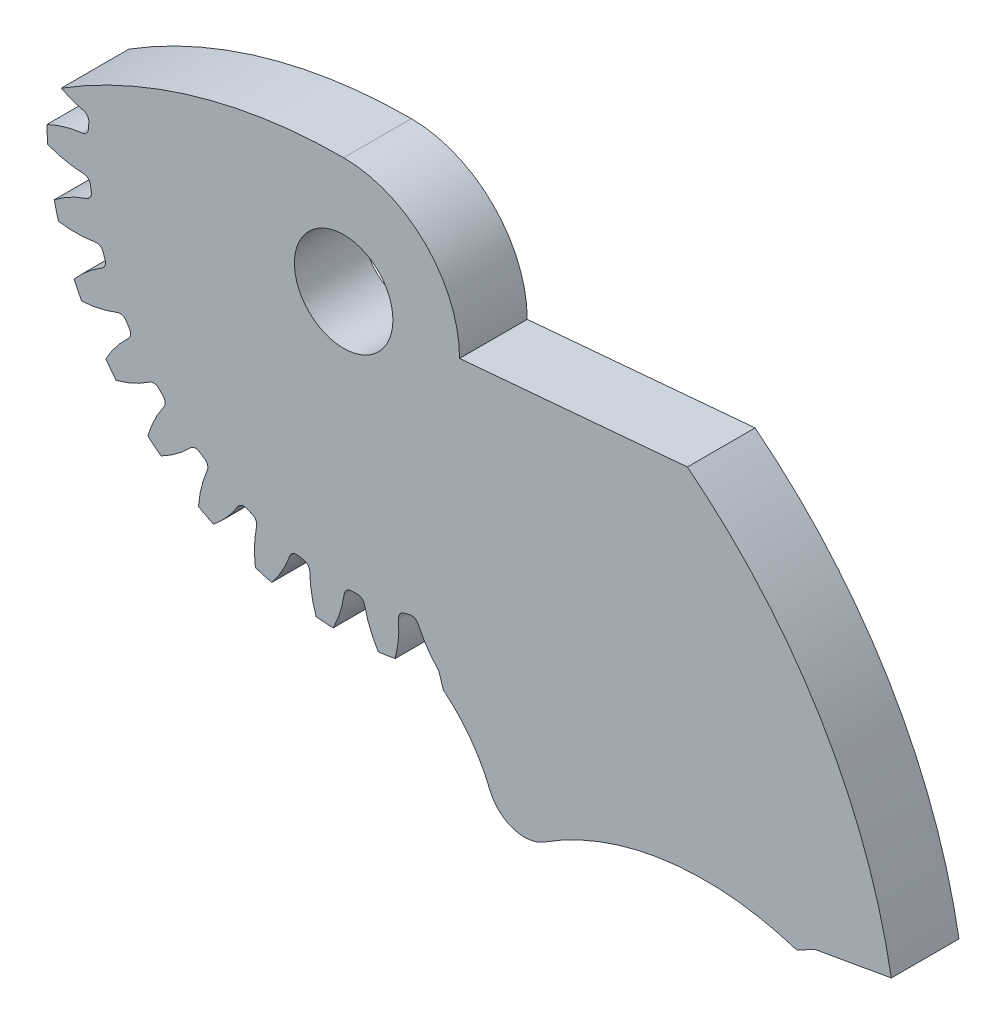
SolidWorks part; units mm, degrees
material "Delrin 2700 NC010, Low Viscosity Acetal Copolymer (SS)"
ref_plane "Front" through (0, 0, 0) normal (0, 0, 1) x (1, 0, 0)
ref_plane "Top" through (0, 0, 0) normal (0, 1, 0) x (1, 0, 0)
ref_plane "Right" through (0, 0, 0) normal (1, 0, 0) x (0, 0, -1)
sketch "Sketch3" plane through (0, 0, 0) normal (0, 0, 1) x (1, 0, 0)
  circle A0 centre (0, 0) radius 40.64
  dimension "od" = 81.28
extrude "gearBody" add sketch "Sketch3" along normal blind 25.4
sketch "Sketch2" plane through (0, 0, 0) normal (0, 0, 1) x (1, 0, 0)
  line L0 (0, 0) -> (34.0786, 14.1158) construction
  line L1 (45.4751, -11.4855) -> (0, 0) construction
  line L2 (0, 0) -> (36.3143, 0) construction
  line L3 (38.0972, -0.458) -> (37.8451, -4.4001) construction
  line L5 (37.9712, -2.4291) -> (0, 0) construction
  line L7 (0, 0) -> (36.8864, 0) construction
  arc A0 (36.879, -0.7403) -> (36.6727, -3.9649) centre (0, 0) ccw construction
  arc A1 (40.637, 0.4947) -> (40.2427, -5.6687) centre (0, 0) ccw construction
  arc A2 (38.0972, -0.458) -> (37.8451, -4.4001) centre (0, 0) ccw construction
  arc A3 (34.9015, -2.6404) -> (34.9534, -1.8283) centre (0, 0) ccw
  arc A4 (45.4751, -11.4855) -> (35.6466, -3.6712) centre (32.0022, -18.3431) ccw
  arc A5 (45.4751, -11.4855) -> (46.5679, 5.5974) centre (0, 0) ccw
  arc A6 (46.5679, 5.5974) -> (35.8238, -0.9008) centre (34.0786, 14.1158) cw
  arc A7 (34.9534, -1.8283) -> (35.8238, -0.9008) centre (35.9376, -1.8798) cw
  arc A8 (35.6466, -3.6712) -> (34.9015, -2.6404) centre (35.8842, -2.7147) cw
  point P6 (46.5679, 5.5974)
  point P22 (45.4751, -11.4855)
  dimension "baseDia" = 73.7729
  dimension "od" = 81.28
  dimension "pd" = 76.2
  dimension "rd" = 70.0024
  dimension "rFillet" = 0.9855
  dimension "pointX" = 46.5679
  dimension "pointY" = 5.5974
  dimension "CTT" = 3.9421
  dimension "flankCenterAngle" = 22.5
extrude "toothCut" cut sketch "Sketch2" along normal through all
pattern_circular "CirPattern1" count 30 over 360 about axis through (0, 0, 25.4) along (0, 0, -1) of "toothCut"
sketch "hub1Dia" plane through (0, 0, 0) normal (0, 0, -1) x (-1, 0, 0)
  circle A0 centre (0, 0) radius 12.7
  dimension "hub1Dia" = 25.4
sketch "hub2Dia" plane through (0, 0, 25.4) normal (0, 0, 1) x (1, 0, 0)
  circle A0 centre (0, 0) radius 12.7
  dimension "hub2dia" = 25.4
sketch "boreDia" plane through (0, 0, 0) normal (0, 0, 1) x (1, 0, 0)
  circle A0 centre (0, 0) radius 9.525
  dimension "boreDia" = 19.05
extrude "bore" cut sketch "boreDia" against normal mid plane 25400
sketch "Sketch4" plane through (0, 0, 25.4) normal (0, 0, 1) x (1, 0, 0)
  circle A0 centre (0, -57.15) radius 76.1746
  arc A2 (-41.7195, 6.5842) -> (41.7195, 6.5842) centre (0, 0) cw
  dimension "D1" = 152.3492
  dimension "D2" = 57.15
extrude "Cut-Extrude1" cut sketch "Sketch4" against normal through all contours A0 region at (0, 26.0638, 25.4)
sketch "Sketch5" plane through (0, 0, 25.4) normal (0, 0, 1) x (1, 0, 0)
  line L0 (0, 19.0246) -> (21.5163, 0.2011)
  line L1 (21.5163, 0.2011) -> (8.9608, -26.928)
  line L2 (8.9608, -26.928) -> (13.028, -38.4952)
  line L3 (0, 0) -> (0, -57.15) construction
  line L4 (0, -57.15) -> (-48.0548, 1.9542) construction
  line L5 (0, -57.15) -> (65.9691, -95.2373) construction
  line L6 (13.6543, -40.4261) -> (13.028, -38.4952)
  line L9 (0, -57.15) -> (75.0173, -43.9224) construction
  line L10 (75.0173, -43.9224) -> (64.5114, -45.7749)
  line L11 (64.5114, -45.7749) -> (62.0894, -47.0863)
  circle A1 centre (0, -57.15) radius 76.1746 construction
  arc A4 (33.1977, 11.4101) -> (-34.0662, 10.9827) centre (0, -57.15) ccw construction
  arc A5 (0, 19.0246) -> (75.0173, -43.9224) centre (0, -57.15) cw
  circle A6 centre (0, -57.15) radius 21.59 construction
  arc A9 (33.1977, 11.4101) -> (-34.0662, 10.9827) centre (0, -57.15) ccw construction
  arc A10 (20.0525, -49.1485) -> (13.6543, -40.4261) centre (0, -57.15) ccw
  circle A12 centre (49.4934, -85.725) radius 40.64 construction
  arc A13 (27.5177, -51.539) -> (62.0894, -47.0863) centre (49.4934, -85.725) cw
  arc A14 (27.5177, -51.539) -> (20.0525, -49.1485) centre (24.7708, -47.2658) cw
  point P28 (21.569, -56.1981)
  dimension "D1" = 43.18
  dimension "D3" = 81.28
  dimension "D7" = 5.08
  dimension "D2" = 120
  dimension "D4" = 57.15
  dimension "D6" = 10.668
  dimension "D5" = 80
extrude "Boss-Extrude1" add sketch "Sketch5" against normal up to surface (25.4 mm away) up to face at (9.525, 0, 0)
sketch "Sketch6" plane through (0, 0, 0) normal (0, 1, 0) x (1, 0, 0)
  line L0 (-46.1384, -9.271) -> (97.8162, -9.271)
  line L4 (97.8162, -9.271) -> (71.9328, -41.1538)
  line L5 (71.9328, -41.1538) -> (-48.6783, -38.0647)
  line L6 (-48.6783, -38.0647) -> (-46.1384, -9.271)
  dimension "D1" = 9.271
extrude "Cut-Extrude2" cut sketch "Sketch6" against normal through all both and the other way through all
sketch "Sketch7" plane through (0, 0, 9.271) normal (0, 0, 1) x (1, 0, 0)
  line L8 (15.875, 0) -> (50.2154, 3.0044)
  line L9 (-43.0106, 8.3498) -> (-40.0828, 3.8911)
  line L10 (0, -57.15) -> (-43.0106, 8.3498) construction
  line L11 (0, 0) -> (80.4469, 0) construction
  arc A0 (-40.2427, 5.6687) -> (-35.6466, 3.6712) centre (-32.0022, 18.3431) ccw construction
  circle A3 centre (0, -57.15) radius 73.025 construction
  circle A4 centre (0, 0) radius 15.875 construction
  arc A5 (0, 15.875) -> (15.875, 0) centre (0, 0) cw
  circle A8 centre (0, -57.15) radius 78.359 construction
  arc A9 (-43.0106, 8.3498) -> (50.2154, 3.0044) centre (0, -57.15) cw
  arc A10 (0, 15.875) -> (-40.0828, 3.8911) centre (0, -57.15) ccw
  point P0 (-36.4485, 3.894)
  dimension "D2" = 57.15
  dimension "D1" = 146.05
  dimension "D3" = 156.718
  dimension "D4" = 5
extrude "Cut-Extrude3" cut sketch "Sketch7" against normal through all both
sketch "Sketch8" plane through (0, 0, 9.271) normal (0, 0, 1) x (1, 0, 0)
  circle A0 centre (0, 0) radius 6.7469
  circle A1 centre (0, 0) radius 10.9012
  dimension "D1" = 13.4937
extrude "Boss-Extrude2" add sketch "Sketch8" against normal up to surface (9.271 mm away) up to face at (9.525, 0, 0)
equation "\"Bodytube_OD\" = 6.17in"
equation "\"Bodytube_ID\" = 5.998in"
equation "\"Fwd_Tube_Length\" = 38in"
equation "\"Mid_Tube_Length\" = 8in"
equation "\"Aft_Section_Length\"= 40in"
equation "\"Mid_Coupler_Length\" = 13in"
equation "\"Aft_Lower_Length\"= 20in"
equation "\"AB_Coupler_OD_Length\"= 1in"
equation "\"AB_Coupling_Section_Length\"= 0.375in"
equation "\"AB_Coupler_Length\"= \"AB_Coupler_OD_Length\" + \"AB_Coupling_Section_Length\" * 2"
equation "\"Cutout_Angle\" = 80"
equation "\"AB_Paddle_Height\" = 0.375in"
equation "\"AB_Coupler_Num_Screws\"= 6"
equation "\"Num_Cutouts\" = 3"
equation "\"AB_Coupler_OD\"= 6.17in"
equation "\"AB_Coupler_ID\"= 5.75in"
equation "\"AB_Coupler_Surface_Diameter\"= 5.998in"
equation "\"AB_Coupling_Screw_Diameter\"= 0.1065in"
equation "\"AB_Central_Bushing_Length\" = .75in"
equation "\"Lead_Screw_Dist\" = 2.25in"
equation "\"Lead_Screw_Diam\" = (27/64)*1in"
equation "\"Lead_Screw_Length\" = (\"Mid_Coupler_Length\" + 2*0.375in + 2*0.5in)"
equation "\"Paddle_Pin_Offset\" = .25in"
equation "\"Paddle_Pin_Radius\" = 2.25in"
equation "\"Fwd_BKHD_From_Top\" = 18in"
equation "\"D1@Sketch4\"=\"Bodytube_ID\""
equation "\"D2@Sketch4\"=\"Paddle_Pin_Radius\""
equation "\"D3@Sketch5\"=\"Paddle_Gear_OD\""
equation "\"D4@Sketch5\"=\"Paddle_Pin_Radius\""
equation "\"Motor_OD\" = 4in"
equation "\"Aft_Upper_Length\"= \"Aft_Section_Length\" - \"Aft_Lower_Length\" - \"AB_Coupler_OD_Length\""
equation "\"Paddle_Gear_OD\" = 3.2in"
equation "\"D5@Sketch5\"=\"Cutout_Angle\""
equation "\"D6@Sketch5\"=\"AB_Coupler_OD\"-\"AB_Coupler_ID\""
equation "\"D1@Sketch7\"=\"AB_Coupler_ID\""
equation "\"D2@Sketch7\"=\"Paddle_Pin_Radius\""
equation "\"D3@Sketch7\"=\"Bodytube_OD\""
